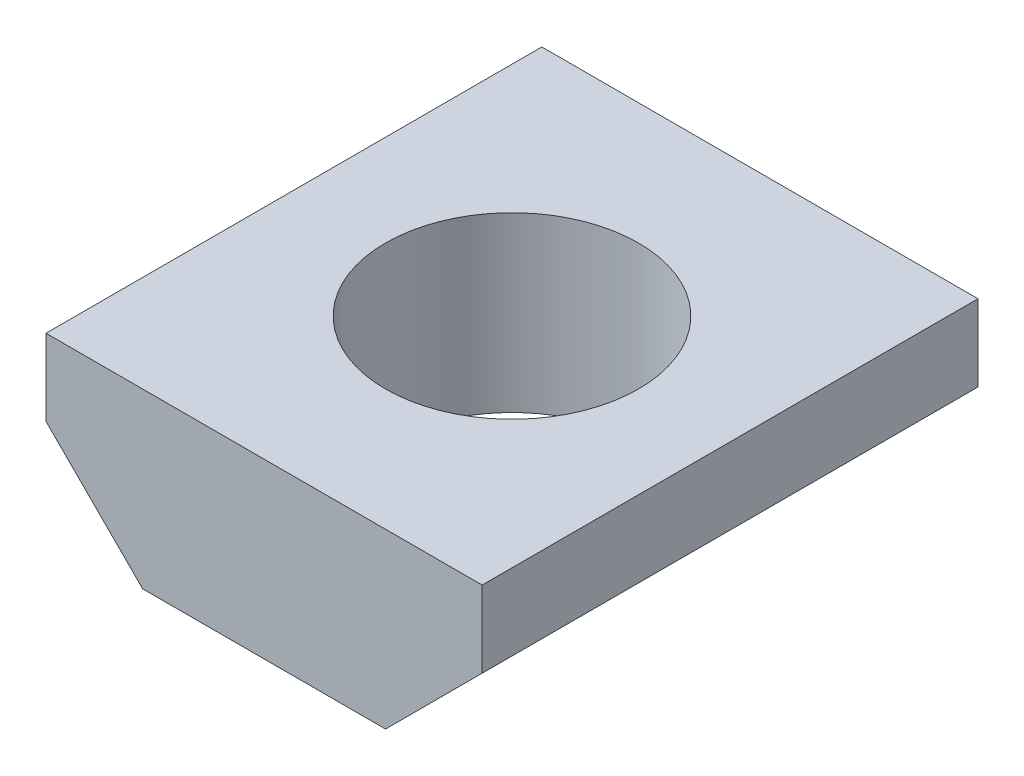
SolidWorks part; units mm, degrees
ref_plane "Front Plane" through (0, 0, 0) normal (0, 0, 1) x (1, 0, 0)
ref_plane "Top Plane" through (0, 0, 0) normal (0, 1, 0) x (1, 0, 0)
ref_plane "Right Plane" through (0, 0, 0) normal (1, 0, 0) x (0, 0, -1)
sketch "Sketch1" plane through (0, 0, 0) normal (0, 0, 1) x (1, 0, 0)
  line L0 (-5.4737, 0) -> (5.4737, 0)
  line L1 (5.4737, 0) -> (5.4737, -1.9177)
  line L2 (5.4737, -1.9177) -> (3.048, -4.3434)
  line L3 (3.048, -4.3434) -> (-3.048, -4.3434)
  line L4 (-3.048, -4.3434) -> (-5.4737, -1.9177)
  line L5 (-5.4737, -1.9177) -> (-5.4737, 0)
  point P5 (0, 0)
  point P8 (5.4737, -19.1419)
  point P9 (-5.4737, -18.2783)
  point P10 (2.3476, -4.3434)
  point P11 (-2.6618, -4.3434)
  point P12 (5.4737, -1.6698)
  point P13 (-5.4737, -1.6698)
  dimension "D1" = 10.9474
  dimension "D2" = 135
  dimension "D3" = 4.3434
  dimension "D4" = 135
  dimension "D5" = 6.096
extrude "Boss-Extrude1" add sketch "Sketch1" along normal blind 12.446
hole_wizard "1/4 (0.25) Diameter Hole1" positions "Sketch2" profile "Sketch3" hole size "1/4" standard "ANSI Inch" end condition through all
sketch "Sketch2" plane through (0, 0, 0) normal (0, 1, 0) x (1, 0, 0)
  point P0 (0, -6.223)
sketch "Sketch3" plane through (0, 0, 6.223) normal (1, 0, 0) x (0, 0, 1)
  line L0 (0, 0) -> (0, 4.3434)
  line L1 (0, 4.3434) -> (3.175, 4.3434)
  line L2 (3.175, 4.3434) -> (3.175, 0)
  line L5 (3.175, 0) -> (0, 0)
  line L11 (0, -6.35) -> (0, 107.95) construction
  dimension "Thru Hole Dia." = 6.35
  dimension "Thru Hole Depth" = 4.3434
